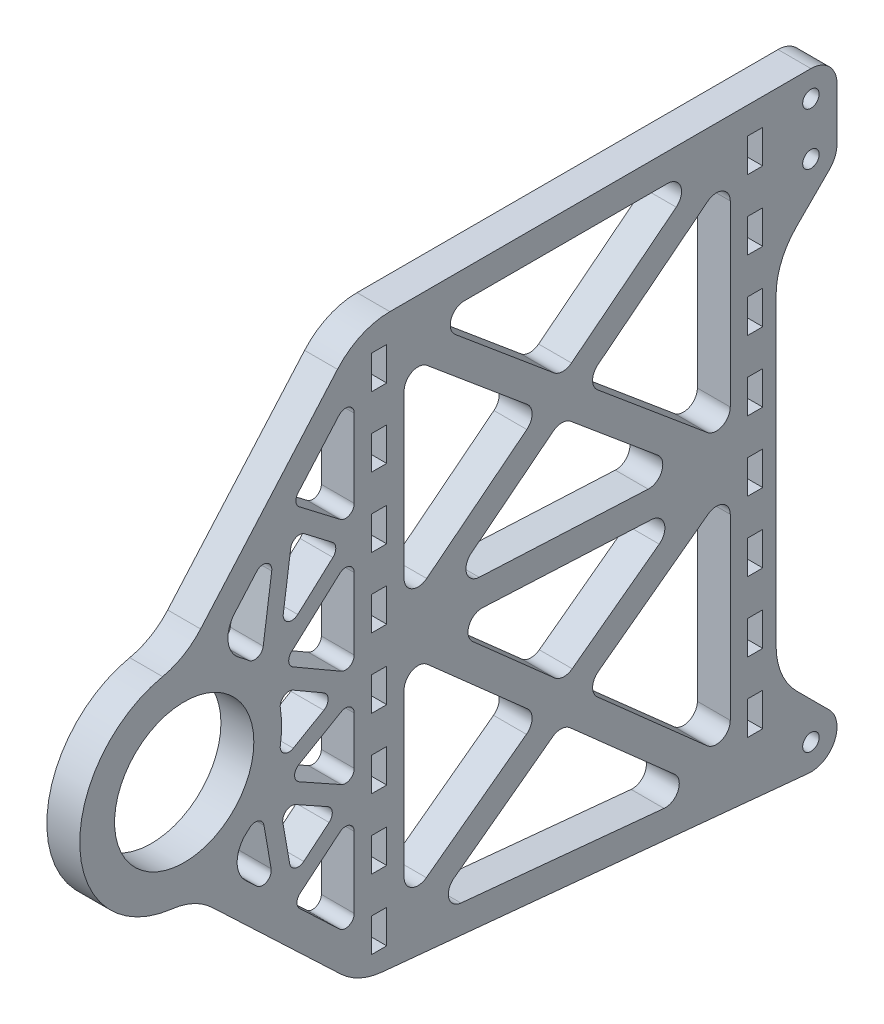
SolidWorks part; units mm, degrees
ref_plane "Front Plane" through (0, 0, 0) normal (0, 0, 1) x (1, 0, 0)
ref_plane "Top Plane" through (0, 0, 0) normal (0, 1, 0) x (1, 0, 0)
ref_plane "Right Plane" through (0, 0, 0) normal (1, 0, 0) x (0, 0, -1)
sketch "PlateGeometry" plane through (0, 0, 0) normal (1, 0, 0) x (0, 0, -1)
  line L1 (-38.1, -76.2) -> (38.1, -76.2) construction
  line L2 (-38.1, -76.2) -> (-38.1, 76.2) construction
  line L3 (-38.1, 76.2) -> (38.1, 76.2) construction
  line L4 (38.1, -76.2) -> (38.1, 76.2) construction
  line L5 (-38.1, -76.2) -> (38.1, 76.2) construction
  line L6 (-38.1, 76.2) -> (38.1, -76.2) construction
  line L11 (31.75, 76.2) -> (-31.75, 76.2) construction
  line L12 (31.75, 76.2) -> (31.75, -76.2) construction
  line L13 (31.75, -76.2) -> (-31.75, -76.2) construction
  line L14 (-31.75, 76.2) -> (-31.75, -76.2) construction
  line L15 (31.75, 76.2) -> (-31.75, -76.2) construction
  line L16 (31.75, -76.2) -> (-31.75, 76.2) construction
  point P0 (0, 0)
  point P9 (0, 0)
  line B0 (-35.7923, -66.6761) -> (-32.7923, -66.6739)
  line B1 (-35.7923, -66.6761) -> (-35.7877, -73.0261)
  line B2 (-35.7877, -73.0261) -> (-32.7877, -73.0239)
  line B3 (-32.7923, -66.6739) -> (-32.7877, -73.0239)
  line B4 (-35.7923, -66.6761) -> (-32.7877, -73.0239) construction
  line B5 (-35.7877, -73.0261) -> (-32.7923, -66.6739) construction
  line B6 (-35.7923, -53.9761) -> (-32.7923, -53.9739)
  line B7 (-35.7923, -53.9761) -> (-35.7877, -60.3261)
  line B8 (-35.7877, -60.3261) -> (-32.7877, -60.3239)
  line B9 (-32.7923, -53.9739) -> (-32.7877, -60.3239)
  line B10 (-35.7877, -60.3261) -> (-32.7923, -53.9739) construction
  line B11 (-35.7923, -41.2761) -> (-32.7923, -41.2739)
  line B12 (-35.7923, -41.2761) -> (-35.7877, -47.6261)
  line B13 (-35.7877, -47.6261) -> (-32.7877, -47.6239)
  line B14 (-32.7923, -41.2739) -> (-32.7877, -47.6239)
  line B15 (-35.7923, -41.2761) -> (-32.7877, -47.6239) construction
  line B16 (-35.7877, -47.6261) -> (-32.7923, -41.2739) construction
  line B17 (-35.7923, -28.5761) -> (-32.7923, -28.5739)
  line B18 (-35.7877, -34.9261) -> (-32.7877, -34.9239)
  line B19 (-32.7923, -28.5739) -> (-32.7877, -34.9239)
  line B20 (-35.7923, -15.8761) -> (-35.7877, -22.2261)
  line B21 (-32.7923, -15.8739) -> (-32.7877, -22.2239)
  line B22 (-35.7923, 9.5239) -> (-32.7923, 9.5261)
  line B23 (-32.7923, 9.5261) -> (-32.7877, 3.1761)
  line B24 (-35.7923, 9.5239) -> (-32.7877, 3.1761) construction
  line B25 (-35.7923, 22.2239) -> (-35.7877, 15.8739)
  line B26 (-35.7923, 34.9239) -> (-35.7877, 28.5739)
  line B27 (-35.7923, 47.6239) -> (-35.7877, 41.2739)
  line B28 (-35.7877, 41.2739) -> (-32.7923, 47.6261) construction
  line B29 (32.7886, -66.6757) -> (32.7914, -73.0257)
  line B30 (32.7914, -73.0257) -> (35.7914, -73.0243)
  line B31 (35.7886, -66.6743) -> (35.7914, -73.0243)
  line B32 (32.7886, -66.6757) -> (35.7914, -73.0243) construction
  line B33 (32.7914, -73.0257) -> (35.7886, -66.6743) construction
  line B34 (32.7886, -53.9757) -> (35.7886, -53.9743)
  line B35 (35.7886, -53.9743) -> (35.7914, -60.3243)
  line B36 (32.7914, -47.6257) -> (35.7914, -47.6243)
  line B37 (35.7886, -41.2743) -> (35.7914, -47.6243)
  line B38 (32.7886, -41.2757) -> (35.7914, -47.6243) construction
  line B39 (32.7886, -28.5757) -> (35.7914, -34.9243) construction
  line B40 (32.7886, -15.8757) -> (32.7914, -22.2257)
  line B41 (32.7886, -3.1757) -> (35.7914, -9.5243) construction
  line B42 (32.7914, -9.5257) -> (35.7886, -3.1743) construction
  line B43 (32.7886, 9.5243) -> (35.7886, 9.5257)
  line B44 (32.7886, 9.5243) -> (32.7914, 3.1743)
  line B45 (32.7914, 3.1743) -> (35.7914, 3.1757)
  line B46 (32.7886, 9.5243) -> (35.7914, 3.1757) construction
  line B47 (32.7886, 22.2243) -> (32.7914, 15.8743)
  line B48 (35.7886, 22.2257) -> (35.7914, 15.8757)
  line B49 (32.7886, 22.2243) -> (35.7914, 15.8757) construction
  line B50 (32.7914, 15.8743) -> (35.7886, 22.2257) construction
  line B51 (32.7914, 41.2743) -> (35.7914, 41.2757)
  line B52 (35.7886, 47.6257) -> (35.7914, 41.2757)
  line B53 (32.7886, 60.3243) -> (32.7914, 53.9743)
  line B54 (35.7886, 60.3257) -> (35.7914, 53.9757)
  line B55 (32.7886, 73.0243) -> (32.7914, 66.6743)
  line B56 (35.7886, 73.0257) -> (35.7914, 66.6757)
  line B57 (32.7914, 66.6743) -> (35.7886, 73.0257) construction
  circle B58 centre (-37.3063, -73.025) radius 5.5563 construction
  circle B59 centre (-37.3063, -73.025) radius 6.8263 construction
  circle B60 centre (-44.9262, -53.975) radius 5.5563 construction
  circle B61 centre (-44.9262, -53.975) radius 6.8263 construction
  dimension "D11" = 63.5
  dimension "D12" = 3.175
  dimension "D1" = 76.2
  dimension "D2" = 152.4
  dimension "D4" = 3.81
  dimension "D5" = 6.35
  dimension "D6" = 12.7
  dimension "D7" = 6.35
  dimension "D8" = 3.81
  dimension "D10" = 12.7
  dimension "D13" = 19.05
  dimension "D14" = 7.62
  dimension "D3" = 12
  dimension "D9" = 12
sketch_block_instance "SlotOutline-1"
sketch_block "SlotOutline" parameters "D1"=18.06, "D2"=7.2935
sketch_block_instance "SlotOutline-2"
sketch_block_instance "SlotOutline-3"
sketch_block_instance "SlotOutline-4"
sketch_block_instance "SlotOutline-5"
sketch_block_instance "SlotOutline-6"
sketch_block_instance "SlotOutline-7"
sketch_block_instance "SlotOutline-8"
sketch_block_instance "SlotOutline-9"
sketch_block_instance "SlotOutline-10"
sketch_block_instance "SlotOutline-11"
sketch_block_instance "SlotOutline-12"
sketch_block_instance "SlotOutline-13"
sketch_block_instance "SlotOutline-14"
sketch_block_instance "SlotOutline-15"
sketch_block_instance "SlotOutline-16"
sketch_block_instance "SlotOutline-17"
sketch_block_instance "SlotOutline-18"
sketch_block_instance "SlotOutline-19"
sketch_block_instance "SlotOutline-20"
sketch_block_instance "SlotOutline-21"
sketch_block_instance "SlotOutline-22"
sketch_block_instance "SlotOutline-23"
sketch_block_instance "SlotOutline-24"
sketch_block_instance "PulleyOutline-1"
sketch_block "PulleyOutline" parameters "D1"=11.1125, "D2"=13.6525
sketch_block_instance "PulleyOutline-2"
sketch "MotorGeometry" plane through (0, 0, 0) normal (1, 0, 0) x (0, 0, -1)
  line L0 (-83.2734, 1.775) -> (-83.2734, 49.025) construction
  line L3 (-50.2786, -55.4665) -> (-63.8121, -13.9087) construction
  line L4 (-41.2645, -76.9242) -> (-75.3216, -19.0975) construction
  line L5 (-38.1, -76.2) -> (-38.1, 76.2) construction
  line L6 (-38.1, -76.2) -> (38.1, -76.2) construction
  line L7 (38.1, -76.2) -> (38.1, 76.2) construction
  line L8 (-83.2734, 17.65) -> (-69.85, 9.9) construction
  line L9 (-69.85, 9.9) -> (-56.4266, 17.65) construction
  line L10 (-56.4266, 17.65) -> (-56.4266, 33.15) construction
  line L11 (-56.4266, 33.15) -> (-69.85, 40.9) construction
  line L12 (-69.85, 40.9) -> (-83.2734, 33.15) construction
  line L13 (-83.2734, 33.15) -> (-83.2734, 17.65) construction
  line L14 (-86.2734, 1.775) -> (-86.2734, 49.025)
  line L15 (-80.2734, 1.775) -> (-80.2734, 49.025)
  line L16 (-56.4266, 1.775) -> (-56.4266, 49.025) construction
  line L17 (-59.4266, 1.775) -> (-59.4266, 49.025)
  line L18 (-53.4266, 1.775) -> (-53.4266, 49.025)
  line L19 (-69.85, 8.3125) -> (-69.85, 47.25) construction
  line L20 (-72.85, 8.3125) -> (-72.85, 47.25)
  line L21 (-66.85, 8.3125) -> (-66.85, 47.25)
  circle A0 centre (44.45, -66.675) radius 1.5
  circle A1 centre (-69.85, -15.875) radius 11
  circle A5 centre (-69.85, -15.875) radius 30 construction
  circle A6 centre (-69.85, -15.875) radius 6.35 construction
  circle A7 centre (-44.9262, -53.975) radius 5.5562 construction
  circle A8 centre (-37.3063, -73.025) radius 5.5562 construction
  circle A9 centre (-69.85, -15.875) radius 25.5 construction
  circle A10 centre (-69.85, 25.4) radius 16 construction
  circle A11 centre (-69.85, 25.4) radius 11.5 construction
  circle A12 centre (-69.85, 25.4) radius 13.4234 construction
  arc A13 (-86.2734, 1.775) -> (-80.2734, 1.775) centre (-83.2734, 1.775) ccw
  arc A14 (-80.2734, 49.025) -> (-86.2734, 49.025) centre (-83.2734, 49.025) ccw
  arc A15 (-59.4266, 1.775) -> (-53.4266, 1.775) centre (-56.4266, 1.775) ccw
  arc A16 (-53.4266, 49.025) -> (-59.4266, 49.025) centre (-56.4266, 49.025) ccw
  arc A17 (-72.85, 8.3125) -> (-66.85, 8.3125) centre (-69.85, 8.3125) ccw
  arc A18 (-66.85, 47.25) -> (-72.85, 47.25) centre (-69.85, 47.25) ccw
  point P29 (-83.2734, 25.4)
  point P39 (-56.4266, 25.4)
  point P46 (-69.85, 27.7812)
  dimension "D1" = 22
  dimension "D4" = 60
  dimension "D5" = 12.7
  dimension "D7" = 4.5
  dimension "D8" = 32
  dimension "D9" = 4.5
  dimension "D13" = 3
  dimension "D3" = 6
  dimension "D2" = 31
  dimension "D6" = 38.1
  dimension "D10" = 31.75
  dimension "D11" = 9.525
  dimension "D12" = 6.35
  dimension "D14" = 15.875
  dimension "D15" = 1.5875
  dimension "D16" = 15.875
  dimension "D17" = 6.35
  dimension "D18" = 41.275
sketch "Sketch4" plane through (0, 0, 0) normal (1, 0, 0) x (0, 0, -1)
  line L0 (49.2125, 25.4) -> (49.2125, 34.925)
  line L1 (47.8176, 22.0324) -> (38.1, 12.3148)
  line L2 (-30.48, -50.8) -> (-38.1, -50.8) construction
  line L3 (-30.48, -50.8) -> (-30.48, -63.5) construction
  line L4 (-30.48, -63.5) -> (-38.1, -63.5) construction
  line L5 (-38.1, -50.8) -> (-38.1, -63.5) construction
  line L6 (-30.48, -50.8) -> (-38.1, -63.5) construction
  line L7 (-30.48, -63.5) -> (-38.1, -50.8) construction
  line L8 (38.1, 12.3148) -> (38.1, -53.5898)
  line L9 (38.1, -53.5898) -> (47.8176, -63.3074)
  line L10 (38.1, -76.2) -> (38.1, 76.2) construction
  line L11 (43.9929, -71.4155) -> (-38.1, -63.5)
  line L12 (-38.1, -63.5) -> (-68.2893, -34.861)
  line L13 (-70.0557, 3.1739) -> (-38.1, 39.6875)
  line L14 (-38.1, -76.2) -> (-38.1, 76.2) construction
  line L15 (-38.1, 39.6875) -> (44.45, 39.6875)
  line L17 (-83.2734, 1.775) -> (-83.2734, 58.55) construction
  line L18 (-86.2734, 1.775) -> (-86.2734, 58.55) construction
  line L19 (-80.2734, 1.775) -> (-80.2734, 58.55) construction
  line L20 (-69.85, 8.3125) -> (-69.85, 53.6) construction
  line L21 (-72.85, 8.3125) -> (-72.85, 53.6) construction
  line L22 (-66.85, 8.3125) -> (-66.85, 53.6) construction
  line L23 (-56.4266, 1.775) -> (-56.4266, 58.55) construction
  line L24 (-59.4266, 1.775) -> (-59.4266, 58.55) construction
  line L25 (-53.4266, 1.775) -> (-53.4266, 58.55) construction
  circle A0 centre (44.45, 25.4) radius 1.5
  circle A1 centre (44.45, 34.925) radius 1.5
  circle A2 centre (44.45, -66.675) radius 4.7625 construction
  circle A3 centre (44.45, 25.4) radius 4.7625 construction
  circle A4 centre (44.45, 34.925) radius 4.7625 construction
  circle A5 centre (-69.85, -15.875) radius 12.7
  arc A6 (43.9929, -71.4155) -> (47.8176, -63.3074) centre (44.45, -66.675) ccw
  circle A7 centre (-69.85, -15.875) radius 19.05
  arc A8 (47.8176, 22.0324) -> (49.2125, 25.4) centre (44.45, 25.4) ccw
  arc A9 (49.2125, 34.925) -> (44.45, 39.6875) centre (44.45, 34.925) ccw
  circle A10 centre (44.45, -66.675) radius 1.5
  arc A11 (-86.2734, 1.775) -> (-80.2734, 1.775) centre (-83.2734, 1.775) ccw construction
  arc A12 (-80.2734, 58.55) -> (-86.2734, 58.55) centre (-83.2734, 58.55) ccw construction
  arc A13 (-72.85, 8.3125) -> (-66.85, 8.3125) centre (-69.85, 8.3125) ccw construction
  arc A14 (-66.85, 53.6) -> (-72.85, 53.6) centre (-69.85, 53.6) ccw construction
  arc A15 (-59.4266, 1.775) -> (-53.4266, 1.775) centre (-56.4266, 1.775) ccw construction
  arc A16 (-53.4266, 58.55) -> (-59.4266, 58.55) centre (-56.4266, 58.55) ccw construction
  arc A17 (-72.85, 24.1875) -> (-66.85, 24.1875) centre (-69.85, 24.1875) cw construction
  arc A18 (-72.85, 33.3625) -> (-66.85, 33.3625) centre (-69.85, 33.3625) ccw construction
  point P12 (-34.29, -57.15)
  point P36 (-83.2734, 30.1625)
  point P47 (-69.85, 30.9562)
  point P55 (-56.4266, 30.1625)
  dimension "D1" = 3
  dimension "D4" = 9.525
  dimension "D9" = 25.4
  dimension "D10" = 38.1
  dimension "D11" = 6
  dimension "D14" = 3.175
  dimension "D2" = 9.525
  dimension "D3" = 101.6
  dimension "D5" = 3.81
  dimension "D6" = 12.7
  dimension "D7" = 45
  dimension "D8" = 45
  dimension "D12" = 12.7
  dimension "D13" = 25.4
  dimension "D15" = 15.875
extrude "Boss-Extrude1" add sketch "Sketch4" along normal mid plane 6 contours L0 A9 L13 A7 L12 L11 A6 L9 L8 L1 A8 A0 A1 | A7 A5 | L24 A15 L25 L13 | L13 A13 L22 region at (0, -13.2133, 6.0048) region at (0, -2.7151, 56.8315)
sketch "Sketch5" plane through (3, 0, 0) normal (1, 0, 0) x (0, 0, -1)
  line B0 (35.665, -54.102) -> (32.915, -54.102)
  line B1 (35.665, -54.102) -> (35.665, -60.198)
  line B2 (35.665, -60.198) -> (32.915, -60.198)
  line B3 (32.915, -54.102) -> (32.915, -60.198)
  line B4 (35.665, -54.102) -> (32.915, -60.198) construction
  line B5 (35.665, -60.198) -> (32.915, -54.102) construction
  line B6 (-32.915, -54.102) -> (-35.665, -54.102)
  line B7 (-32.915, -54.102) -> (-32.915, -60.198)
  line B8 (-32.915, -60.198) -> (-35.665, -60.198)
  line B9 (-35.665, -54.102) -> (-35.665, -60.198)
  line B10 (-32.915, -54.102) -> (-35.665, -60.198) construction
  line B11 (-32.915, -60.198) -> (-35.665, -54.102) construction
sketch_block_instance "Slot-1"
sketch_block "Slot" parameters "D1"=11.2845, "D2"=5.6739
sketch_block_instance "Slot-2"
extrude "LowerSlot" cut sketch "Sketch5" against normal through all both and the other way through all contours B0 B3 B2 B1 region at (3, -57.15, -34.29)
extrude "UpperSlot" cut sketch "Sketch5<3>" against normal through all both and the other way through all contours B6 B9 B8 B7 region at (3, -57.15, 34.29)
sketch "Sketch5<3>" plane through (3, 0, 0) normal (1, 0, 0) x (0, 0, -1) same geometry as "Sketch5"
pattern_linear "LowerSlots" count 8 spacing 12.7 along (0, 1, 0) of "LowerSlot"
pattern_linear "UpperSlots" count 8 spacing 12.7 along (0, 1, 0) of "UpperSlot"
sketch "Sketch6" plane through (3, 0, 0) normal (1, 0, 0) x (0, 0, -1)
  line L0 (-38.84, 7.4417) -> (-54.5614, -6.7982) construction
  line L1 (-54.5614, -6.7982) -> (-38.84, -15.875) construction
  line L2 (-38.84, -15.875) -> (-54.5614, -24.9518) construction
  line L3 (-54.5614, -24.9518) -> (-38.84, -33.7118) construction
  line L4 (-38.84, -15.875) -> (-52.07, -15.875) construction
  line L5 (-51.2473, 16.9514) -> (-54.5614, -6.7982) construction
  line L6 (-54.5614, -24.9518) -> (-51.2473, -44.0256) construction
  line L8 (29.74, -64.9377) -> (29.74, 34.6075)
  line L9 (-29.74, -59.2025) -> (-29.74, 34.6075)
  line L10 (-38.84, 31.1284) -> (-38.84, -55.7958)
  line L11 (-32.915, -54.102) -> (-32.915, -60.198) construction
  line L12 (-35.665, -54.102) -> (-35.665, -60.198) construction
  line L13 (32.915, -54.102) -> (32.915, -60.198) construction
  line L14 (29.74, -15.1651) -> (-29.74, -12.2975) construction
  line L15 (29.74, -64.9377) -> (-29.74, -12.2975) construction
  line L16 (44.1325, 25.5315) -> (44.1325, 34.6075)
  line L17 (44.1325, 34.6075) -> (-35.7952, 34.6075)
  line L18 (-35.7952, 34.6075) -> (-67.873, -2.0456)
  line L19 (-66.5997, -29.4616) -> (-35.8722, -58.6113)
  line L20 (-35.8722, -58.6113) -> (43.6001, -66.2741)
  line L21 (43.6001, -66.2741) -> (33.02, -55.694)
  line L22 (33.02, -55.694) -> (33.02, 14.419)
  line L23 (33.02, 14.419) -> (44.1325, 25.5315)
  line L24 (44.1325, 25.5315) -> (44.1325, 34.6075)
  line L25 (44.1325, 34.6075) -> (-35.7952, 34.6075)
  line L26 (-35.7952, 34.6075) -> (-67.873, -2.0456)
  line L27 (-66.5997, -29.4616) -> (-35.8722, -58.6113)
  line L28 (-35.8722, -58.6113) -> (43.6001, -66.2741)
  line L29 (43.6001, -66.2741) -> (33.02, -55.694)
  line L30 (33.02, -55.694) -> (33.02, 14.419)
  line L31 (33.02, 14.419) -> (44.1325, 25.5315)
  line L32 (-29.74, -12.2975) -> (29.74, 34.6075) construction
  line L33 (29.74, -15.1651) -> (-29.74, 34.6075) construction
  line L34 (-29.74, -59.2025) -> (29.74, -15.1651) construction
  line L35 (-51.2473, -44.0256) -> (-38.84, -33.7118) construction
  line L39 (-38.84, 7.4417) -> (-51.2473, 16.9514) construction
  line L44 (-56.695, -21.9456) -> (-52.3418, -46.9999)
  line L45 (-52.3418, -46.9999) -> (-36.0444, -33.4522)
  line L46 (-56.695, -21.9456) -> (-36.0444, -33.4522)
  line L47 (-55.3552, -8.1731) -> (-42.015, -15.875)
  line L48 (-42.015, -15.875) -> (-55.3552, -23.5769)
  line L49 (-52.4432, 19.8681) -> (-56.7383, -10.9119)
  line L50 (-36.363, 7.5434) -> (-52.4432, 19.8681)
  line L51 (-36.363, 7.5434) -> (-56.7383, -10.9119)
  line L52 (-52.4278, -27.9579) -> (-50.1528, -41.0514)
  line L53 (-50.1528, -41.0514) -> (-41.6356, -33.9713)
  line L54 (-52.4278, -27.9579) -> (-41.6356, -33.9713)
  line L55 (-53.7677, -5.4234) -> (-35.665, -15.875)
  line L56 (-35.665, -15.875) -> (-53.7677, -26.3266)
  line L57 (-50.0515, 14.0346) -> (-52.3845, -2.6846)
  line L58 (-41.317, 7.3401) -> (-50.0515, 14.0346)
  line L59 (-41.317, 7.3401) -> (-52.3845, -2.6846)
  line L60 (28.0566, -66.8398) -> (-31.4234, -14.1996)
  line L61 (-31.3128, -10.303) -> (28.1672, 36.602)
  line L62 (28.11, -17.113) -> (-31.37, 32.6595)
  line L63 (-31.2514, -57.1611) -> (28.2286, -13.1237)
  line L64 (29.6177, -17.7021) -> (-29.8623, -14.8346)
  line L65 (31.4234, -63.0356) -> (-28.0566, -10.3954)
  line L66 (-28.1672, -14.292) -> (31.3128, 32.613)
  line L67 (31.37, -13.2171) -> (-28.11, 36.5555)
  line L68 (-28.2286, -61.2439) -> (31.2514, -17.2065)
  line L69 (29.8623, -12.628) -> (-29.6177, -9.7605)
  arc A5 (-58.6124, -37.0388) -> (-58.3903, -29.4693) centre (-55.1161, -33.3533) cw
  circle A6 centre (-69.85, -15.875) radius 17.78
  circle A7 centre (-69.85, -15.875) radius 17.78
  arc A8 (-67.873, -2.0456) -> (-66.5997, -29.4616) centre (-69.85, -15.875) ccw
  arc A9 (-67.873, -2.0456) -> (-66.5997, -29.4616) centre (-69.85, -15.875) ccw
  arc A10 (-59.6996, -1.2771) -> (-60.6223, 6.2393) centre (-56.7995, 2.8937) cw
  dimension "D6" = 5.08
  dimension "D2" = 3.175
  dimension "D3" = 3.175
  dimension "D4" = 3.175
  dimension "D7" = 60
  dimension "D1" = 5.08
  dimension "D5" = 5.08
  dimension "D8" = 1.5875
  dimension "D9" = 1.5875
  dimension "D10" = 2.54
  dimension "D11" = 2.54
extrude "Cut-Extrude1" cut sketch "Sketch6" against normal through all both and the other way through all contours L45 L27 L10 | L54 L52 L53 | L10 L56 L46 | A7 A5 L27 L44 | A7 L48 L47 | L51 L55 L10 | L59 L58 L57 | A10 A7 L49 L26 | L50 L10 L26 region at (3, -45.566, 42.5892) region at (3, -24.8433, 43.008) region at (3, -34.2808, 56.7363) region at (3, -5.0849, 43.1871) region at (3, 19.5729, 42.6265) region at (3, -15.875, 48.9797) region at (3, 4.3105, 57.3434) region at (3, -34.3269, 48.0721) region at (3, 6.23, 47.9176)
extrude "Cut-Extrude2" cut sketch "Sketch6<3>" against normal through all both and the other way through all contours L68 L28 L60 | L9 L63 L60 | L68 L65 L8 | L65 L63 L64 | L69 L62 L66 | L61 L62 L9 | L67 L8 L66 | L67 L61 L25 region at (3, -39.2947, -20.8764) region at (3, -55.0641, 0.5163) region at (3, -22.3709, 0.2933) region at (3, -36.4642, 21.4644) region at (3, 9.9735, -20.8752) region at (3, -5.0548, 0.4832) region at (3, 27.6489, 0.3262) region at (3, 10.9169, 21.4633)
sketch "Sketch6<3>" plane through (3, 0, 0) normal (1, 0, 0) x (0, 0, -1) same geometry as "Sketch6"
fillet "Fillet1" radius 1.5875 25 edges at (0, 9.4419, 38.84) (0, 31.1284, 38.84) (0, 18.1485, 50.1996) (0, 14.7725, 53.1543) (0, 7.3401, 41.317) (0, 14.0346, 50.0515) (0, -2.6846, 52.3845) (0, -6.5125, 51.8813) (0, -14.0419, 38.84) (0, 5.2998, 38.84) (0, -22.3955, 53.3088) (0, -15.875, 42.015) (0, -9.3545, 53.3088) (0, -42.1954, 53.1766) (0, -17.7081, 38.84) (0, -24.9272, 51.3439) (0, -31.8945, 38.84) (0, -27.9579, 52.4278) (0, -41.0514, 50.1528) (0, -33.9713, 41.6356) (0, -55.7958, 38.84) (0, -35.7761, 38.84) (0, -45.1259, 50.0875)
fillet "Fillet2" radius 2.54 24 edges at (0, 13.7316, 0.8346) (0, 34.6075, -25.638) (0, 34.6075, 25.7821) (0, -11.8531, -29.74) (0, 31.3727, -29.74) (0, 10.4009, -3.1457) (0, 10.5178, 4.9099) (0, 31.2955, 29.74) (0, -9.0628, 29.74) (0, -12.2642, -22.3154) (0, 7.1871, 0.9296) (0, -10.0874, 22.8354) (0, -34.5711, 0.7397) (0, -17.3594, -22.5076) (0, -15.1824, 22.6477) (0, -38.0127, -3.1491) (0, -61.5458, -29.74) (0, -18.3255, -29.74) (0, -56.0421, 29.74) (0, -37.6611, 4.9133) (0, -59.5667, 25.9632) (0, -64.5229, -25.4388) (0, -41.1027, 1.0245) (0, -15.6894, 29.74)
fillet "Fillet3" radius 12.7 6 edges at (0, 12.3148, -38.1) (0, -53.5898, -38.1) (0, 39.6875, 38.1) (0, 3.1739, 70.0557) (0, -34.861, 68.2893) (0, -63.5, 38.1)
